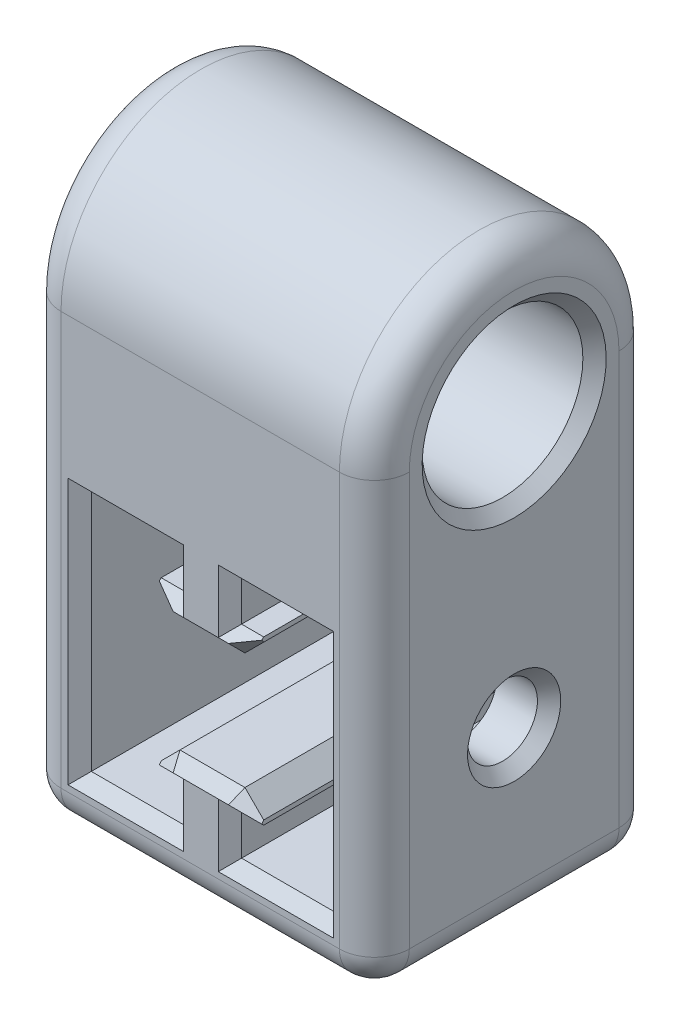
SolidWorks part; units mm, degrees
ref_plane "Front Plane" through (0, 0, 0) normal (0, 0, 1) x (1, 0, 0)
ref_plane "Top Plane" through (0, 0, 0) normal (0, 1, 0) x (1, 0, 0)
ref_plane "Right Plane" through (0, 0, 0) normal (1, 0, 0) x (0, 0, -1)
sketch "Sketch1" plane through (0, 0, 0) normal (0, 0, 1) x (1, 0, 0)
  line L0 (0, -15) -> (0, 15) construction
  line L1 (0, 15) -> (14.8993, 15)
  line L2 (14.8993, 15) -> (14.8993, -14.9496)
  line L3 (14.8993, -14.9496) -> (-15, -14.9496)
  line L4 (-15, -14.9496) -> (-15, 15)
  line L5 (-15, 15) -> (0, 15)
  line L6 (0, -10.4) -> (0, 10.4) construction
  line L7 (0, 10.4) -> (-10.4, 10.4) construction
  line L8 (-10.4, 10.4) -> (-2.5, 10.4)
  line L9 (-2.5, 10.4) -> (-2.5, 7)
  line L10 (-2.5, 7) -> (0, 7) construction
  line L11 (-2.5, 7) -> (-4.4, 7)
  line L12 (-4.4, 7) -> (-4.4, 6.61)
  line L13 (-4.4, 6.61) -> (-2.79, 5)
  line L14 (-2.79, 5) -> (0, 5) construction
  line L15 (-2.79, 5) -> (2.79, 5)
  line L16 (10.4, 2.9336) -> (10.4, -2.9336)
  line L22 (-10.4, 10.4) -> (-10.4, 2.9336)
  line L23 (0, 0) -> (-11.0308, 0) construction
  line L24 (4.4, 6.61) -> (2.79, 5)
  line L25 (4.4, 7) -> (4.4, 6.61)
  line L26 (2.5, 7) -> (4.4, 7)
  line L27 (2.5, 10.4) -> (2.5, 7)
  line L28 (10.4, 10.4) -> (2.5, 10.4)
  line L29 (10.4, 10.4) -> (10.4, 2.9336)
  line L35 (-10.4, -10.4) -> (0, 0) construction
  line L36 (-2.79, -5) -> (0, -5) construction
  line L37 (-2.5, -7) -> (0, -7) construction
  line L38 (0, -10.4) -> (-10.4, -10.4) construction
  line L43 (10.4, -10.4) -> (10.4, -2.9336)
  line L44 (10.4, -10.4) -> (2.5, -10.4)
  line L45 (2.5, -10.4) -> (2.5, -7)
  line L46 (2.5, -7) -> (4.4, -7)
  line L47 (4.4, -7) -> (4.4, -6.61)
  line L48 (4.4, -6.61) -> (2.79, -5)
  line L49 (-10.4, -10.4) -> (-10.4, -2.9336)
  line L54 (-2.79, -5) -> (2.79, -5)
  line L55 (-4.4, -6.61) -> (-2.79, -5)
  line L56 (-4.4, -7) -> (-4.4, -6.61)
  line L57 (-2.5, -7) -> (-4.4, -7)
  line L58 (-2.5, -10.4) -> (-2.5, -7)
  line L59 (-10.4, -10.4) -> (-2.5, -10.4)
  line L60 (-10.4, 2.9336) -> (-10.4, -2.61)
  line L61 (-10.4, -2.61) -> (-10.4, -2.9336)
  point P43 (5, 0)
  point P58 (-5, 0)
  dimension "D1" = 2.5
  dimension "D2" = 2.79
  dimension "D3" = 1.9
  dimension "D4" = 135
  dimension "D5" = 2
  dimension "D6" = 15
  dimension "D7" = 15
  dimension "D8" = 10.4
  dimension "D9" = 90
  dimension "D10" = 3.4
  dimension "D11" = 10.4
extrude "Boss-Extrude1" add sketch "Sketch1" along normal blind 24
sketch "Sketch5" plane through (-15, 0, 0) normal (-1, 0, 0) x (0, 0, 1)
  line L2 (0, 15) -> (24, 15)
  line L10 (0, 23.5) -> (0, 15)
  line L11 (12, 17) -> (12, 23.5) construction
  line L13 (24, 23.5) -> (24, 15)
  circle A2 centre (12, 23.5) radius 6.9
  arc A3 (0, 23.5) -> (24, 23.5) centre (12, 23.5) cw
  dimension "D3" = 13.8
  dimension "D5" = 6.5
  dimension "D4" = 2
  dimension "D6" = 12
extrude "Boss-Extrude3" add sketch "Sketch5" against normal through all
sketch "Sketch3" plane through (-15, 0, 0) normal (-1, 0, 0) x (0, 0, 1)
  line L0 (12, 0) -> (24, 4.2752) construction
  line L2 (0, 0) -> (12, 0) construction
  line L3 (24, 23.5) -> (24, -14.9496) construction
  circle A0 centre (12, 0) radius 3
extrude "Cut-Extrude1" cut sketch "Sketch3" against normal through all
sketch "Sketch6" plane through (-15, 0, 0) normal (-1, 0, 0) x (0, 0, 1)
  line L0 (12.4334, 16.6136) -> (12, 23.5) construction
  circle A0 centre (12, 23.5) radius 6.9 construction
  circle A1 centre (12, 23.5) radius 5
  circle A2 centre (12, 23.5) radius 12
extrude "Boss-Extrude4" add sketch "Sketch6" against normal blind 4
fillet "Fillet1" radius 3 10 edges at (-0.0504, -14.9496, 24) (14.8993, 4.2752, 24) (-15, 4.2752, 24) (14.8993, 4.2752, 0) (-15, 4.2752, 0) (-0.0504, -14.9496, 0) (14.8993, -14.9496, 12) (-15, -14.9496, 12) (-15, 35.5, 12) (14.8993, 35.5, 12)
chamfer "Chamfer1" distance 1 angle 45 44 edges at (-15, 0, 15) (14.8993, 0, 15) (14.8993, 23.5, 18.9) (-3.595, 5.805, 0) (0, 5, 0) (3.595, 5.805, 0) (3.45, 7, 0) (2.5, 8.7, 0) (6.45, 10.4, 0) (10.4, 0, 0) (6.45, -10.4, 0) (2.5, -8.7, 0) (3.45, -7, 0) (3.595, -5.805, 0) (0, -5, 0) (-3.595, -5.805, 0) (-3.45, -7, 0) (-2.5, -8.7, 0) (-6.45, -10.4, 0) (-10.4, 0, 0) (-6.45, 10.4, 0) (-2.5, 8.7, 0) (-3.45, 7, 0) (-2.5, 8.7, 24) (-6.45, 10.4, 24) (-10.4, 0, 24) (-6.45, -10.4, 24) (-2.5, -8.7, 24) (-3.45, -7, 24) (-3.595, -5.805, 24) (0, -5, 24) (3.595, -5.805, 24) (3.45, -7, 24) (2.5, -8.7, 24) (6.45, -10.4, 24) (10.4, 0, 24) (6.45, 10.4, 24) (2.5, 8.7, 24) (3.45, 7, 24) (3.595, 5.805, 24) (0, 5, 24) (-3.595, 5.805, 24) (-3.45, 7, 24) (-15, 23.5, 17)
